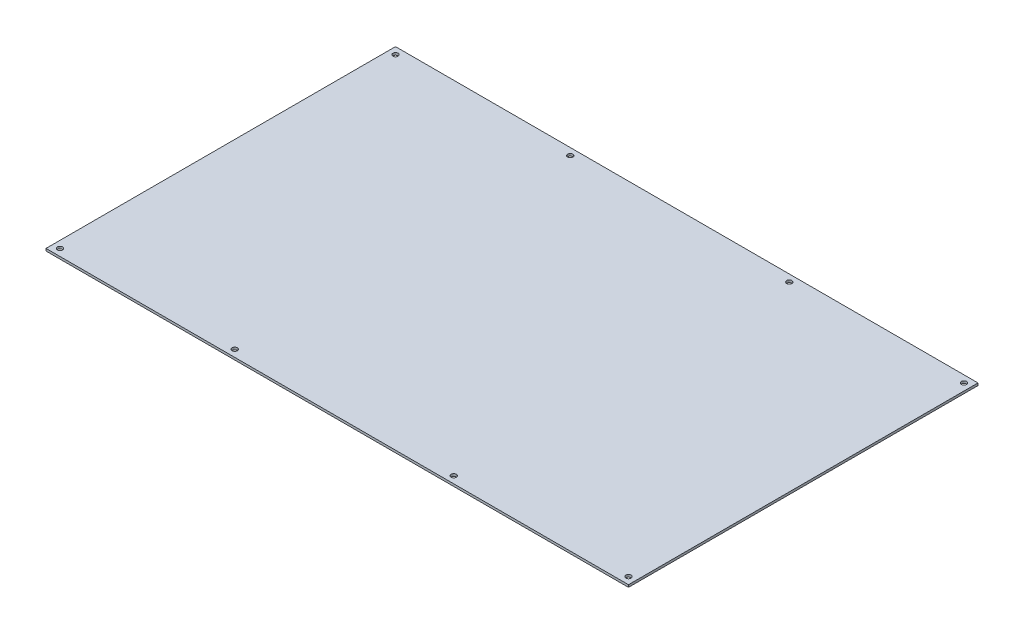
SolidWorks part; units mm, degrees
material "1060-H16"
ref_plane "Front Plane" through (0, 0, 0) normal (0, 0, 1) x (1, 0, 0)
ref_plane "Top Plane" through (0, 0, 0) normal (0, 1, 0) x (1, 0, 0)
ref_plane "Right Plane" through (0, 0, 0) normal (1, 0, 0) x (0, 0, -1)
sketch "Sketch1" plane through (0, 0, 0) normal (0, 1, 0) x (1, 0, 0)
  line L0 (-250, -150) -> (-245, -150) construction
  line L1 (-250, -150) -> (250, -150)
  line L2 (-250, -150) -> (-250, 150)
  line L3 (-250, 150) -> (250, 150)
  line L4 (250, -150) -> (250, 150)
  line L5 (-250, -150) -> (250, 150) construction
  line L6 (-250, 150) -> (250, -150) construction
  line L7 (-245, -150) -> (-245, -165) construction
  line L8 (-245, -165) -> (245, -165) construction
  line L9 (245, -165) -> (245, -150) construction
  line L10 (245, -150) -> (250, -150) construction
  line L11 (250, -150) -> (250, -145) construction
  line L12 (250, -145) -> (265, -145) construction
  line L13 (265, -145) -> (265, 145) construction
  line L14 (265, 145) -> (250, 145) construction
  line L15 (250, 145) -> (250, 150) construction
  line L16 (250, 150) -> (245, 150) construction
  line L17 (245, 150) -> (245, 165) construction
  line L18 (245, 165) -> (-245, 165) construction
  line L19 (-245, 165) -> (-245, 150) construction
  line L20 (-245, 150) -> (-250, 150) construction
  line L21 (-250, 150) -> (-250, 145) construction
  line L22 (-250, 145) -> (-265, 145) construction
  line L23 (-265, 145) -> (-265, -145) construction
  line L24 (-265, -145) -> (-250, -145) construction
  line L25 (-250, -145) -> (-250, -150) construction
  point P0 (0, 0)
  dimension "D1" = 500
  dimension "D2" = 300
  dimension "D3" = 15
  dimension "D4" = 5
base flange "Base-Flange1" sketch "Sketch1" thickness 2 reverse thickness direction no parameters "D1"=1
hole_wizard "M4 Clearance Hole1" positions "Sketch2" profile "Sketch3" hole size "M4" standard "DIN" end condition up to next
sketch "Sketch2" plane through (0, 0, 0) normal (0, 1, 0) x (1, 0, 0)
  line L0 (250, 150) -> (-250, 150) construction
  line L1 (-250, 150) -> (-250, -150) construction
  line L2 (250, -150) -> (250, 150) construction
  line L3 (-250, -150) -> (250, -150) construction
  point P0 (244, 144)
  point P2 (94, 144)
  point P4 (-94, 144)
  point P6 (-244, 144)
  point P8 (-244, -144)
  point P10 (-94, -144)
  point P12 (94, -144)
  point P14 (244, -144)
  dimension "D1" = 6
  dimension "D2" = 6
  dimension "D3" = 150
  dimension "D4" = 150
  dimension "D5" = 6
  dimension "D6" = 6
sketch "Sketch3" plane through (244, 0, -144) normal (1, 0, 0) x (0, 0, 1)
  line L0 (0, 0) -> (0, 2)
  line L1 (0, 2) -> (2.25, 2)
  line L2 (2.25, 2) -> (2.25, 0)
  line L5 (2.25, 0) -> (0, 0)
  line L11 (0, -6.35) -> (0, 107.95) construction
  dimension "Thru Hole Dia." = 4.5
  dimension "Thru Hole Depth" = 2
sketch "Bend-Lines1" [suppressed] plane through (0, 0, 0) normal (0, 1, 0) x (1, 0, 0)
sketch "Bounding-Box1" [suppressed] plane through (0, 0, 0) normal (0, 1, 0) x (1, 0, 0)
sheet metal parameters "Sheet-Metal1" thickness 2 parameters "D1"=1
flat pattern "Flat-Pattern1" [suppressed]
sketch "Bend-Lines2" plane through (0, 0, 0) normal (0, 1, 0) x (1, 0, 0)
sketch3d "Bounding-Box2" [suppressed]
  line L0 (250, 150, 0) -> (-250, 150, 0) construction
  line L1 (250, -150, 0) -> (-250, -150, 0) construction
  line L2 (250, 150, 0) -> (250, -150, 0) construction
  line L3 (-250, 150, 0) -> (-250, -150, 0) construction
sheet metal parameters "Sheet-Metal3" thickness 2 parameters "D1"=1
flat pattern "Flat-Pattern1"
sketch "Bend-Lines2" plane through (0, 0, 0) normal (0, 1, 0) x (1, 0, 0)
sketch3d "Bounding-Box2" [suppressed]
  line L0 (250, 150, 0) -> (-250, 150, 0) construction
  line L1 (250, -150, 0) -> (-250, -150, 0) construction
  line L2 (250, 150, 0) -> (250, -150, 0) construction
  line L3 (-250, 150, 0) -> (-250, -150, 0) construction
